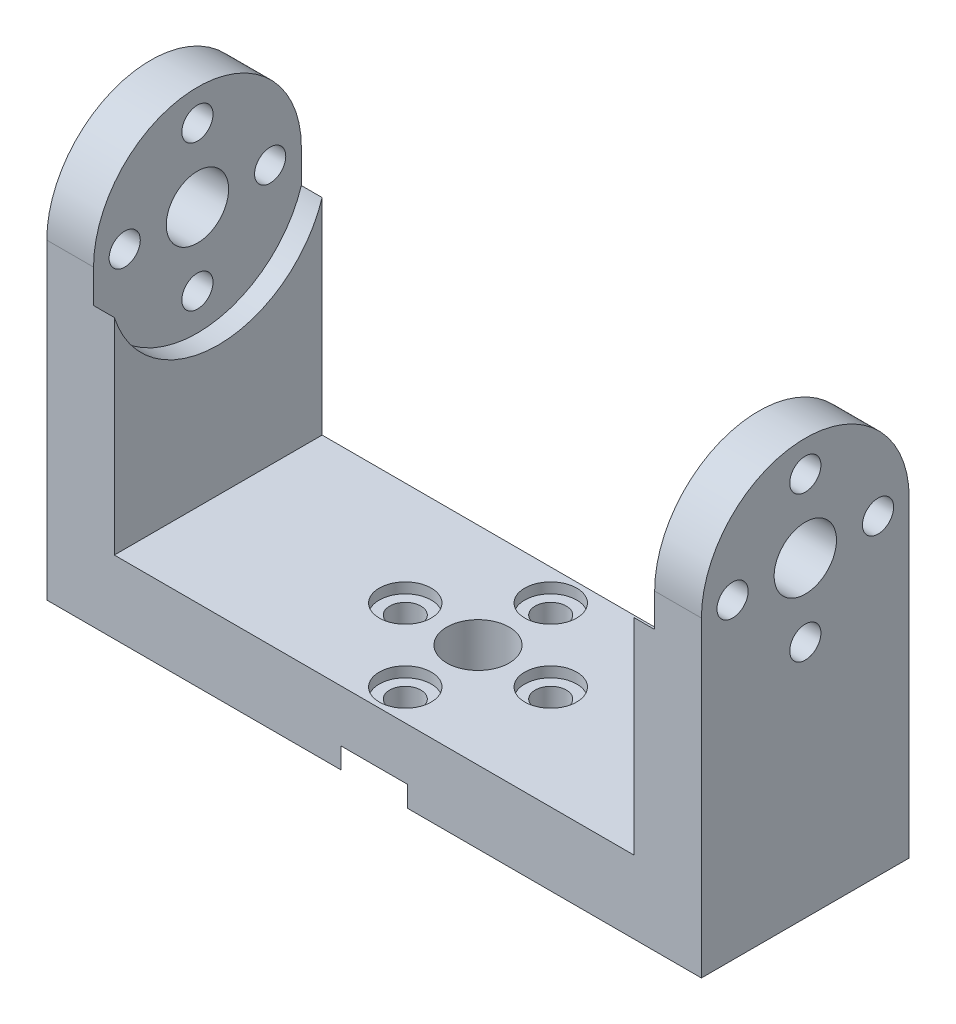
SolidWorks part; units mm, degrees
ref_plane "Alzado" through (0, 0, 0) normal (0, 0, 1) x (1, 0, 0)
ref_plane "Planta" through (0, 0, 0) normal (0, 1, 0) x (1, 0, 0)
ref_plane "Vista lateral" through (0, 0, 0) normal (1, 0, 0) x (0, 0, -1)
sketch "Croquis1" plane through (0, 0, 0) normal (0, 1, 0) x (1, 0, 0)
  line L1 (25, -10) -> (-25, -10)
  line L2 (25, -10) -> (25, 10)
  line L3 (25, 10) -> (-25, 10)
  line L4 (-25, -10) -> (-25, 10)
  line L5 (25, -10) -> (-25, 10) construction
  line L6 (25, 10) -> (-25, -10) construction
  circle A0 centre (0, 0) radius 3
  point P0 (0, 0)
extrude "Saliente-Extruir1" add sketch "Croquis1" along normal blind 5
sketch "Croquis2" plane through (0, 0, 0) normal (0, -1, 0) x (1, 0, 0)
  circle A0 centre (0, 0) radius 10.5
extrude "Cortar-Extruir7" cut sketch "Croquis2" against normal blind 2
sketch "Croquis7" plane through (0, 2, 0) normal (0, -1, 0) x (1, 0, 0)
  circle A0 centre (0, 0) radius 7 construction
  circle A1 centre (0, 7) radius 1.5
  circle A2 centre (7, 0) radius 1.5
  circle A3 centre (0, -7) radius 1.5
  circle A4 centre (-7, 0) radius 1.5
extrude "Cortar-Extruir8" cut sketch "Croquis7" against normal blind 4
sketch "Croquis8" plane through (0, 5, 0) normal (0, 1, 0) x (1, 0, 0)
  circle A0 centre (0, 7) radius 2.5
  circle A1 centre (7, 0) radius 2.5
  circle A2 centre (0, -7) radius 2.5
  circle A3 centre (-7, 0) radius 2.5
  point P12 (0, 0)
  dimension "D1" = 4
extrude "Cortar-Extruir9" cut sketch "Croquis8" against normal blind 1
sketch "Croquis9" plane through (0, 5, 0) normal (0, 1, 0) x (1, 0, 0)
  line L0 (-25, -10) -> (25, -10) construction
  line L1 (25, 10) -> (20, 10)
  line L2 (25, 10) -> (25, -10)
  line L3 (25, -10) -> (20, -10)
  line L4 (20, 10) -> (20, -10)
  line L5 (25, 10) -> (-25, 10) construction
  line L6 (-25, -10) -> (-20, -10)
  line L7 (-25, -10) -> (-25, 10)
  line L8 (-25, 10) -> (-20, 10)
  line L9 (-20, -10) -> (-20, 10)
extrude "Saliente-Extruir3" add sketch "Croquis9" along normal blind 33
sketch "Croquis10" plane through (25, 0, 0) normal (1, 0, 0) x (0, 0, -1)
  line L0 (0, 38) -> (0, 0) construction
  line L1 (-10, 38) -> (10, 38) construction
  line L2 (0, 0) -> (0, 38) construction
  line L3 (0, 38) -> (0, 28) construction
  line L4 (10, 38) -> (10, 0) construction
  line L5 (-10, 38) -> (-10, 0) construction
  line L6 (10, 28) -> (21.899, 31.2218)
  line L7 (21.899, 31.2218) -> (12.8892, 40.9135)
  line L8 (12.8892, 40.9135) -> (-22.2074, 40.0122)
  line L9 (-22.2074, 40.0122) -> (-10, 28)
  circle A0 centre (0, 28) radius 3
  arc A1 (10, 28) -> (-10, 28) centre (0, 28) ccw
extrude "Cortar-Extruir10" cut sketch "Croquis10" against normal blind 50
sketch "Croquis11" plane through (-20, 0, 0) normal (1, 0, 0) x (0, 0, -1)
  circle A0 centre (0, 28) radius 10.5
extrude "Cortar-Extruir11" cut sketch "Croquis11" against normal blind 2 and the other way blind 42
sketch "Croquis12" plane through (-22, 0, 0) normal (1, 0, 0) x (0, 0, -1)
  circle A0 centre (0, 28) radius 7 construction
  circle A1 centre (0, 35) radius 1.5
  circle A2 centre (7, 28) radius 1.5
  circle A3 centre (0, 21) radius 1.5
  circle A4 centre (-7, 28) radius 1.5
  point P14 (0, 28)
  dimension "D1" = 4
extrude "Cortar-Extruir12" cut sketch "Croquis12" against normal blind 6 and the other way blind 50
sketch "Croquis13" plane through (25, 0, 0) normal (1, 0, 0) x (0, 0, -1)
  line L3 (10, 0) -> (10, 28)
  line L4 (-10, 28) -> (-10, 0)
  line L5 (-10, 0) -> (10, 0)
  line L6 (10, 0) -> (10, 28)
  line L7 (-10, 28) -> (-10, 0)
  line L8 (-10, 0) -> (10, 0)
  circle A0 centre (-7, 28) radius 1.5 construction
  arc A1 (10, 28) -> (-10, 28) centre (0, 28) ccw
  arc A2 (10, 28) -> (-10, 28) centre (0, 28) ccw
  circle A3 centre (0, 28) radius 3 construction
  circle A4 centre (7, 28) radius 1.5 construction
  circle A5 centre (0, 35) radius 1.5 construction
  circle A6 centre (0, 21) radius 1.5 construction
  circle A7 centre (-7, 28) radius 1.5
  circle A8 centre (0, 28) radius 3
  circle A9 centre (7, 28) radius 1.5
  circle A10 centre (0, 35) radius 1.5
  circle A11 centre (0, 21) radius 1.5
  dimension "D1" = 0
extrude "Saliente-Extruir4" add sketch "Croquis13" along normal blind 5
sketch "Croquis14" plane through (-25, 0, 0) normal (-1, 0, 0) x (0, 0, 1)
  line L3 (10, 0) -> (10, 28)
  line L4 (-10, 28) -> (-10, 0)
  line L5 (-10, 0) -> (10, 0)
  line L6 (10, 0) -> (10, 28)
  line L7 (-10, 28) -> (-10, 0)
  line L8 (-10, 0) -> (10, 0)
  circle A0 centre (0, 21) radius 1.5 construction
  arc A1 (10, 28) -> (-10, 28) centre (0, 28) ccw
  arc A2 (10, 28) -> (-10, 28) centre (0, 28) ccw
  circle A3 centre (0, 28) radius 3 construction
  circle A4 centre (-7, 28) radius 1.5 construction
  circle A5 centre (0, 35) radius 1.5 construction
  circle A6 centre (7, 28) radius 1.5 construction
  circle A7 centre (0, 21) radius 1.5
  circle A8 centre (0, 28) radius 3
  circle A9 centre (-7, 28) radius 1.5
  circle A10 centre (0, 35) radius 1.5
  circle A11 centre (7, 28) radius 1.5
  dimension "D1" = 0
extrude "Saliente-Extruir5" add sketch "Croquis14" along normal blind 5
sketch "Croquis15" plane through (-20, 0, 0) normal (1, 0, 0) x (0, 0, -1)
  line L3 (-10, 24.7984) -> (-10, 5)
  line L4 (-10, 5) -> (10, 5)
  line L5 (10, 5) -> (10, 24.7984)
  line L6 (-10, 24.7984) -> (-10, 5)
  line L7 (-10, 5) -> (10, 5)
  line L8 (10, 5) -> (10, 24.7984)
  arc A1 (-10, 24.7984) -> (10, 24.7984) centre (0, 28) ccw
  arc A2 (-10, 24.7984) -> (10, 24.7984) centre (0, 28) ccw
  dimension "D1" = 0
extrude "Cortar-Extruir14" cut sketch "Croquis15" against normal blind 5 and the other way blind 45
sketch "Croquis16" plane through (-22, 0, 0) normal (1, 0, 0) x (0, 0, -1)
  line L2 (-10, 28) -> (-10, 24.7984)
  line L3 (10, 24.7984) -> (10, 28)
  line L4 (-10, 28) -> (-10, 24.7984)
  line L5 (10, 24.7984) -> (10, 28)
  arc A2 (-10, 24.7984) -> (10, 24.7984) centre (0, 28) ccw
  arc A3 (10, 28) -> (-10, 28) centre (0, 28) ccw
  arc A4 (-10, 24.7984) -> (10, 24.7984) centre (0, 28) ccw
  arc A5 (10, 28) -> (-10, 28) centre (0, 28) ccw
  dimension "D1" = 0
extrude "Cortar-Extruir15" cut sketch "Croquis16" against normal blind 5 and the other way blind 49
sketch "Croquis17" plane through (0, 0, 0) normal (0, -1, 0) x (1, 0, 0)
  line L3 (30, 10) -> (3.2016, 10)
  line L4 (3.2016, -10) -> (30, -10)
  line L5 (30, -10) -> (30, 10)
  line L6 (30, 10) -> (3.2016, 10)
  line L7 (3.2016, -10) -> (30, -10)
  line L8 (30, -10) -> (30, 10)
  line L9 (-30, -10) -> (-3.2016, -10)
  line L10 (-3.2016, 10) -> (-30, 10)
  line L11 (-30, 10) -> (-30, -10)
  line L12 (-30, -10) -> (-3.2016, -10)
  line L13 (-3.2016, 10) -> (-30, 10)
  line L14 (-30, 10) -> (-30, -10)
  arc A1 (3.2016, -10) -> (3.2016, 10) centre (0, 0) ccw
  arc A2 (3.2016, -10) -> (3.2016, 10) centre (0, 0) ccw
  arc A3 (-3.2016, 10) -> (-3.2016, -10) centre (0, 0) ccw
  arc A4 (-3.2016, 10) -> (-3.2016, -10) centre (0, 0) ccw
  dimension "D1" = 0
  dimension "D2" = 0
extrude "Saliente-Extruir6" add sketch "Croquis17" along normal blind 2
sketch "Croquis18" plane through (0, 2, 0) normal (0, -1, 0) x (1, 0, 0)
  line L2 (3.2016, 10) -> (-3.2016, 10)
  line L3 (-3.2016, -10) -> (3.2016, -10)
  line L4 (3.2016, 10) -> (-3.2016, 10)
  line L5 (-3.2016, -10) -> (3.2016, -10)
  circle A0 centre (0, 0) radius 3 construction
  circle A1 centre (0, 0) radius 3
  arc A2 (-3.2016, 10) -> (-3.2016, -10) centre (0, 0) ccw
  arc A3 (3.2016, -10) -> (3.2016, 10) centre (0, 0) ccw
  arc A4 (-3.2016, 10) -> (-3.2016, -10) centre (0, 0) ccw
  arc A5 (3.2016, -10) -> (3.2016, 10) centre (0, 0) ccw
  circle A6 centre (7, 0) radius 1.5 construction
  circle A7 centre (7, 0) radius 1.5
  circle A8 centre (0, 7) radius 1.5 construction
  circle A9 centre (0, 7) radius 1.5
  circle A10 centre (-7, 0) radius 1.5 construction
  circle A11 centre (-7, 0) radius 1.5
  circle A12 centre (0, -7) radius 1.5 construction
  circle A13 centre (0, -7) radius 1.5
  dimension "D1" = 0
extrude "Saliente-Extruir7" add sketch "Croquis18" along normal blind 2
sketch "Croquis19" plane through (30, 0, 0) normal (1, 0, 0) x (0, 0, -1)
  line L3 (-10, 28) -> (-10, -2)
  line L4 (-10, -2) -> (10, -2)
  line L5 (10, -2) -> (10, 28)
  line L6 (-10, 28) -> (-10, -2)
  line L7 (-10, -2) -> (10, -2)
  line L8 (10, -2) -> (10, 28)
  circle A0 centre (7, 28) radius 1.5 construction
  arc A1 (10, 28) -> (-10, 28) centre (0, 28) ccw
  arc A2 (10, 28) -> (-10, 28) centre (0, 28) ccw
  circle A3 centre (0, 21) radius 1.5 construction
  circle A4 centre (0, 28) radius 3 construction
  circle A5 centre (-7, 28) radius 1.5 construction
  circle A6 centre (0, 35) radius 1.5 construction
  circle A7 centre (7, 28) radius 1.5
  circle A8 centre (0, 21) radius 1.5
  circle A9 centre (0, 28) radius 3
  circle A10 centre (-7, 28) radius 1.5
  circle A11 centre (0, 35) radius 1.5
  dimension "D1" = 0
extrude "Saliente-Extruir8" add sketch "Croquis19" along normal blind 1.5
sketch "Croquis20" plane through (-30, 0, 0) normal (-1, 0, 0) x (0, 0, 1)
  line L3 (-10, 28) -> (-10, -2)
  line L4 (-10, -2) -> (10, -2)
  line L5 (10, -2) -> (10, 28)
  line L6 (-10, 28) -> (-10, -2)
  line L7 (-10, -2) -> (10, -2)
  line L8 (10, -2) -> (10, 28)
  circle A0 centre (0, 21) radius 1.5 construction
  arc A1 (10, 28) -> (-10, 28) centre (0, 28) ccw
  arc A2 (10, 28) -> (-10, 28) centre (0, 28) ccw
  circle A3 centre (0, 28) radius 3 construction
  circle A4 centre (7, 28) radius 1.5 construction
  circle A5 centre (0, 35) radius 1.5 construction
  circle A6 centre (-7, 28) radius 1.5 construction
  circle A7 centre (0, 21) radius 1.5
  circle A8 centre (0, 28) radius 3
  circle A9 centre (7, 28) radius 1.5
  circle A10 centre (0, 35) radius 1.5
  circle A11 centre (-7, 28) radius 1.5
  dimension "D1" = 0
extrude "Saliente-Extruir9" add sketch "Croquis20" along normal blind 1.5
